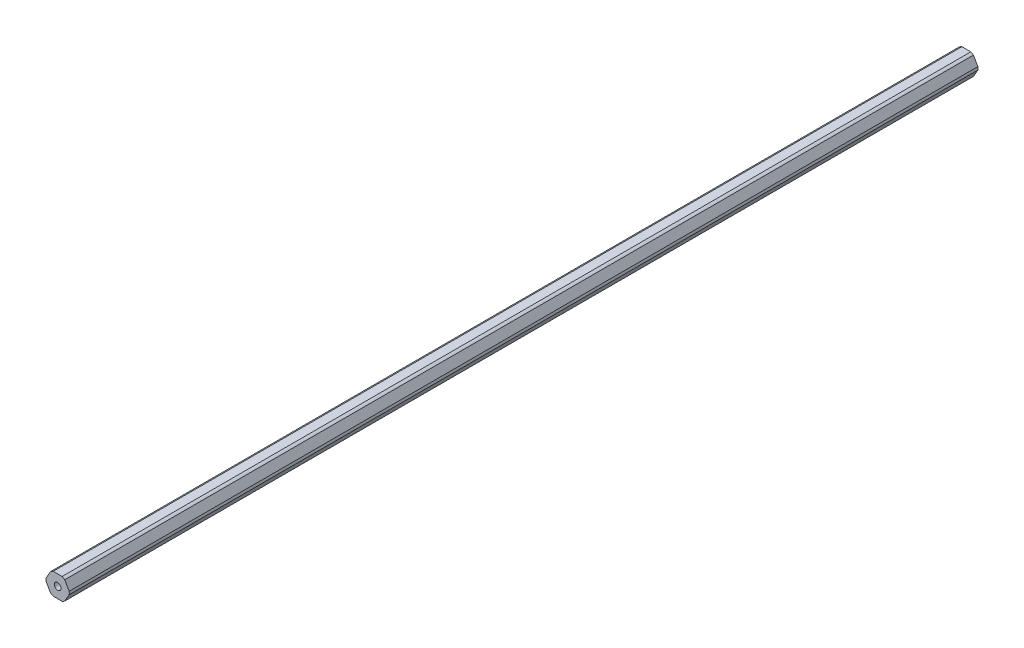
SolidWorks part; units mm, degrees
material "6061-T6 (SS)"
ref_plane "Front Plane" through (0, 0, 0) normal (0, 0, 1) x (1, 0, 0)
ref_plane "Top Plane" through (0, 0, 0) normal (0, 1, 0) x (1, 0, 0)
ref_plane "Right Plane" through (0, 0, 0) normal (1, 0, 0) x (0, 0, -1)
sketch "Sketch1" plane through (0, 0, 0) normal (0, 0, 1) x (1, 0, 0)
  line L1 (7.3323, 0) -> (3.6662, 6.35)
  line L2 (3.6662, 6.35) -> (-3.6662, 6.35)
  line L3 (-3.6662, 6.35) -> (-7.3323, 0)
  line L4 (-7.3323, 0) -> (-3.6662, -6.35)
  line L5 (-3.6662, -6.35) -> (3.6662, -6.35)
  line L6 (3.6662, -6.35) -> (7.3323, 0)
  circle A0 centre (0, 0) radius 6.35 construction
  circle A1 centre (0, 0) radius 6.875
  circle A2 centre (0, 0) radius 2
  point P1 (0, 6.35)
  dimension "D2" = 13.75
  dimension "D3" = 4
  dimension "D1" = 12.7
extrude "Boss-Extrude1" add sketch "Sketch1" along normal blind 536.575 contours L1 A1 L2 L3 L4 L5 L6 A2 region at (6.6736, 0.4353, 0)
equation "\"D2@Sketch1\"=13.75mm"
equation "\"D3@Sketch1\"=4mm"
